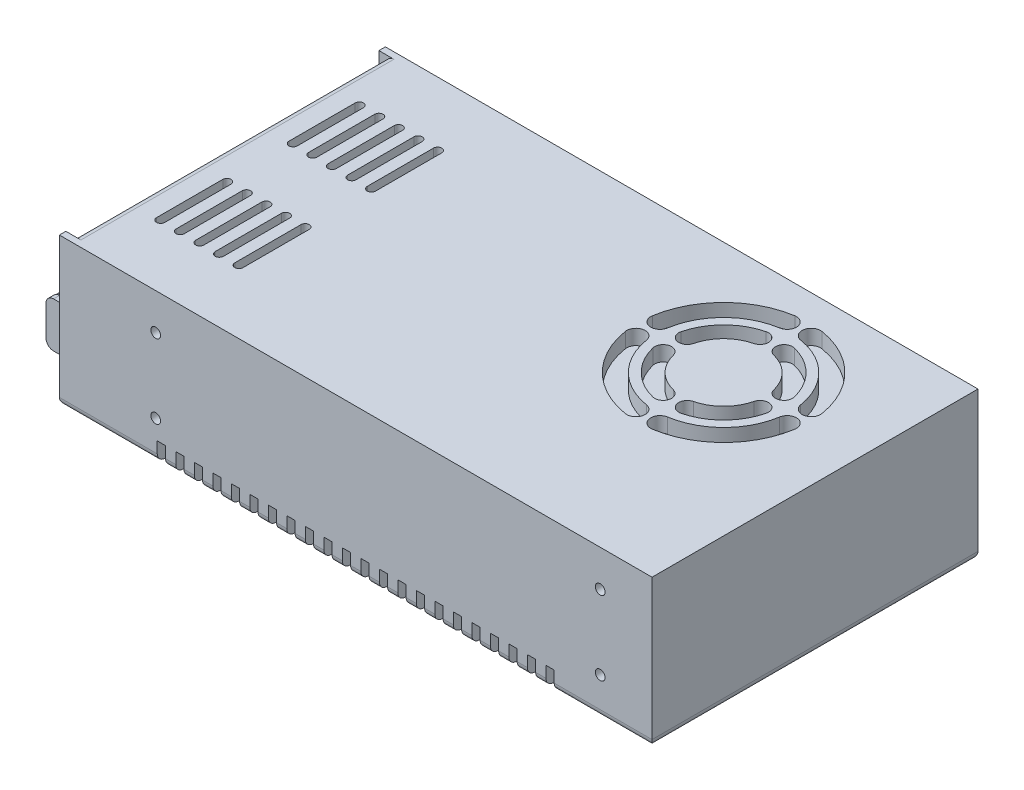
SolidWorks part; units mm, degrees
ref_plane "Front Plane" through (0, 0, 0) normal (0, 0, 1) x (1, 0, 0)
ref_plane "Top Plane" through (0, 0, 0) normal (0, 1, 0) x (1, 0, 0)
ref_plane "Right Plane" through (0, 0, 0) normal (1, 0, 0) x (0, 0, -1)
sketch "Sketch1" plane through (0, 0, 0) normal (0, 1, 0) x (1, 0, 0)
  line L1 (-100, -55) -> (100, -55)
  line L2 (-100, -55) -> (-100, 55)
  line L3 (-100, 55) -> (100, 55)
  line L4 (100, -55) -> (100, 55)
  line L5 (-100, -55) -> (100, 55) construction
  line L6 (-100, 55) -> (100, -55) construction
  point P0 (0, 0)
  dimension "D1" = 110
  dimension "D2" = 200
extrude "Boss-Extrude1" add sketch "Sketch1" along normal blind 50
sketch "Sketch2" plane through (0, 50, 0) normal (0, 1, 0) x (1, 0, 0)
  line L0 (-100, 55) -> (-100, -55) construction
  line L1 (-100, 52.8156) -> (-97.46, 52.8156)
  line L2 (-100, 52.8156) -> (-100, -52.8156)
  line L3 (-100, -52.8156) -> (-97.46, -52.8156)
  line L4 (-97.46, 52.8156) -> (-97.46, -52.8156)
  line L5 (-100, -55) -> (100, -55) construction
  line L6 (100, 55) -> (-100, 55) construction
  dimension "D1" = 2.1844
  dimension "D2" = 2.1844
  dimension "D3" = 2.54
extrude "Cut-Extrude1" cut sketch "Sketch2" against normal blind 41.91
sketch "Sketch3" plane through (-97.46, 0, 0) normal (-1, 0, 0) x (0, 0, 1)
  line L1 (-40.3008, 24.4602) -> (49.1072, 24.4602)
  line L2 (-40.3008, 24.4602) -> (-40.3008, 9.2202)
  line L3 (-40.3008, 9.2202) -> (49.1072, 9.2202)
  line L4 (49.1072, 24.4602) -> (49.1072, 9.2202)
  line L7 (-55, 0) -> (55, 0) construction
  line L8 (55, 50) -> (55, 0) construction
  dimension "D1" = 9.2202
  dimension "D2" = 5.8928
  dimension "D3" = 15.24
  dimension "D4" = 89.408
extrude "Boss-Extrude2" add sketch "Sketch3" along normal blind 12.7
sketch "Sketch4" plane through (-97.46, 0, 0) normal (-1, 0, 0) x (0, 0, 1)
  line L0 (-52.8156, 8.09) -> (-52.8156, 50) construction
  line L1 (-40.3008, 9.2202) -> (-52.8156, 9.2202)
  line L2 (49.1072, 9.2202) -> (49.1072, 24.4602)
  line L3 (49.1072, 24.4602) -> (-40.3008, 24.4602)
  line L4 (-52.8156, 9.2202) -> (-52.8156, 27.0002)
  line L5 (-52.8156, 27.0002) -> (52.8156, 27.0002)
  line L6 (52.8156, 8.09) -> (52.8156, 50) construction
  line L7 (52.8156, 27.0002) -> (52.8156, 9.2202)
  line L8 (52.8156, 9.2202) -> (49.1072, 9.2202)
  line L9 (-40.3008, 24.4602) -> (-40.3008, 9.2202)
  dimension "D1" = 17.78
extrude "Cut-Extrude3" cut sketch "Sketch4" against normal blind 25.4 contours L5 L7 L8 L2 L3 L9 L1 L4
sketch "Sketch5" plane through (0, 9.2202, 0) normal (0, 1, 0) x (1, 0, 0)
  line L0 (-97.46, 40.3008) -> (-97.46, 52.8156) construction
  line L1 (-96.19, 45.7036) -> (-89.84, 45.7036)
  line L2 (-96.19, 45.7036) -> (-96.19, 36.8136)
  line L3 (-96.19, 36.8136) -> (-89.84, 36.8136)
  line L4 (-89.84, 45.7036) -> (-89.84, 36.8136)
  dimension "D1" = 6.35
  dimension "D2" = 1.27
  dimension "D3" = 8.89
  dimension "D4" = 7.112
extrude "Boss-Extrude3" add sketch "Sketch5" along normal blind 8.89
sketch "Sketch6" plane through (0, 24.4602, 0) normal (0, 1, 0) x (1, 0, 0)
  line L0 (-110.16, -49.1072) -> (-110.16, 40.3008) construction
  line L1 (-110.16, 38.2688) -> (-102.032, 38.2688)
  line L2 (-110.16, 38.2688) -> (-110.16, 30.1408)
  line L3 (-110.16, 30.1408) -> (-102.032, 30.1408)
  line L4 (-102.032, 38.2688) -> (-102.032, 30.1408)
  line L5 (-110.16, 40.3008) -> (-72.06, 40.3008) construction
  line L6 (-110.16, 28.6168) -> (-102.032, 28.6168)
  line L7 (-110.16, 28.6168) -> (-110.16, 20.4888)
  line L8 (-110.16, 20.4888) -> (-102.032, 20.4888)
  line L9 (-102.032, 28.6168) -> (-102.032, 20.4888)
  line L10 (-110.16, 18.9648) -> (-102.032, 18.9648)
  line L11 (-110.16, 18.9648) -> (-110.16, 10.8368)
  line L12 (-110.16, 10.8368) -> (-102.032, 10.8368)
  line L13 (-102.032, 18.9648) -> (-102.032, 10.8368)
  line L14 (-110.16, 9.3128) -> (-102.032, 9.3128)
  line L15 (-110.16, 9.3128) -> (-110.16, 1.1848)
  line L16 (-110.16, 1.1848) -> (-102.032, 1.1848)
  line L17 (-102.032, 9.3128) -> (-102.032, 1.1848)
  line L18 (-110.16, -0.3392) -> (-102.032, -0.3392)
  line L19 (-110.16, -0.3392) -> (-110.16, -8.4672)
  line L20 (-110.16, -8.4672) -> (-102.032, -8.4672)
  line L21 (-102.032, -0.3392) -> (-102.032, -8.4672)
  line L22 (-110.16, -9.9912) -> (-102.032, -9.9912)
  line L23 (-110.16, -9.9912) -> (-110.16, -18.1192)
  line L24 (-110.16, -18.1192) -> (-102.032, -18.1192)
  line L25 (-102.032, -9.9912) -> (-102.032, -18.1192)
  line L26 (-110.16, -19.6432) -> (-102.032, -19.6432)
  line L27 (-110.16, -19.6432) -> (-110.16, -27.7712)
  line L28 (-110.16, -27.7712) -> (-102.032, -27.7712)
  line L29 (-102.032, -19.6432) -> (-102.032, -27.7712)
  line L30 (-110.16, -29.2952) -> (-102.032, -29.2952)
  line L31 (-110.16, -29.2952) -> (-110.16, -37.4232)
  line L32 (-110.16, -37.4232) -> (-102.032, -37.4232)
  line L33 (-102.032, -29.2952) -> (-102.032, -37.4232)
  line L35 (-110.16, -38.9472) -> (-102.032, -38.9472)
  line L36 (-110.16, -38.9472) -> (-110.16, -47.0752)
  line L37 (-110.16, -47.0752) -> (-102.032, -47.0752)
  line L38 (-102.032, -38.9472) -> (-102.032, -47.0752)
  line L39 (-110.16, -49.1072) -> (-72.06, -49.1072) construction
  dimension "D1" = 2.032
  dimension "D2" = 8.128
  dimension "D3" = 8.128
  dimension "D5" = 2.032
  dimension "D4" = 9
extrude "Cut-Extrude4" cut sketch "Sketch6" against normal through all
sketch "Sketch8" plane through (-102.032, 0, 0) normal (-1, 0, 0) x (0, 0, 1)
  line L0 (-30.1408, 9.2202) -> (-38.2688, 9.2202) construction
  line L2 (47.0752, 24.4602) -> (38.9472, 24.4602) construction
  circle A0 centre (-34.2048, 16.8402) radius 1.905
  circle A1 centre (-24.5528, 16.8402) radius 1.905
  circle A2 centre (-14.9008, 16.8402) radius 1.905
  circle A3 centre (-5.2488, 16.8402) radius 1.905
  circle A4 centre (4.4032, 16.8402) radius 1.905
  circle A5 centre (14.0552, 16.8402) radius 1.905
  circle A6 centre (23.7072, 16.8402) radius 1.905
  circle A7 centre (33.3592, 16.8402) radius 1.905
  circle A8 centre (43.0112, 16.8402) radius 1.905
  point P4 (-34.2048, 9.2202)
  point P23 (43.0112, 24.4602)
  dimension "D1" = 3.81
  dimension "D2" = 7.62
  dimension "D3" = 9
extrude "Boss-Extrude4" add sketch "Sketch8" along normal blind 2.54
sketch "Sketch9" plane through (-104.572, 0, 0) normal (-1, 0, 0) x (0, 0, 1)
  circle A0 centre (-34.2048, 16.8402) radius 3.81
  circle A1 centre (-24.5528, 16.8402) radius 3.81
  circle A2 centre (-14.9008, 16.8402) radius 3.81
  circle A3 centre (-5.2488, 16.8402) radius 3.81
  circle A4 centre (4.4032, 16.8402) radius 3.81
  circle A5 centre (14.0552, 16.8402) radius 3.81
  circle A6 centre (23.7072, 16.8402) radius 3.81
  circle A7 centre (33.3592, 16.8402) radius 3.81
  circle A12 centre (43.0112, 16.8402) radius 3.81
  dimension "D1" = 7.62
extrude "Boss-Extrude5" add sketch "Sketch9" along normal blind 3.81
fillet "Fillet1" radius 1.27 9 edges at (-108.382, 16.8402, -30.3948) (-108.382, 16.8402, 8.2132) (-108.382, 16.8402, 46.8212) (-108.382, 16.8402, 37.1692) (-108.382, 16.8402, 27.5172) (-108.382, 16.8402, 17.8652) (-108.382, 16.8402, -1.4388) (-108.382, 16.8402, -11.0908) (-108.382, 16.8402, -20.7428)
sketch "Sketch10" plane through (0, 50, 0) normal (0, 1, 0) x (1, 0, 0)
  line L0 (100, 55) -> (-100, 55) construction
  line L1 (100, -55) -> (100, 55) construction
  line L2 (77.771, 20.964) -> (77.771, 12.836) construction
  line L3 (52.248, 48.006) -> (52.248, -12.056) construction
  line L4 (77.771, 16.9) -> (52.248, 16.9) construction
  line L5 (56.312, 42.423) -> (48.184, 42.423) construction
  line L6 (26.725, 20.964) -> (26.725, 12.836) construction
  arc A0 (65.8045, 20.2739) -> (55.6219, 30.4565) centre (52.248, 16.9) ccw
  arc A1 (71.3503, 21.6541) -> (57.0021, 36.0023) centre (52.248, 16.9) ccw
  arc A2 (74.6982, 20.4747) -> (55.8227, 39.3502) centre (52.248, 16.9) ccw
  arc A3 (80.8438, 21.4533) -> (56.8013, 45.4958) centre (52.248, 16.9) ccw
  arc A4 (74.6982, 20.4747) -> (80.8438, 21.4533) centre (77.771, 20.964) ccw
  arc A5 (56.8013, 45.4958) -> (55.8227, 39.3502) centre (56.312, 42.423) ccw
  arc A6 (57.0021, 36.0023) -> (55.6219, 30.4565) centre (56.312, 33.2294) ccw
  arc A7 (65.8045, 13.5261) -> (71.3503, 12.1459) centre (68.5774, 12.836) cw
  arc A8 (65.8045, 20.2739) -> (71.3503, 21.6541) centre (68.5774, 20.964) ccw
  arc A9 (57.0021, -2.2023) -> (55.6219, 3.3435) centre (56.312, 0.5706) cw
  arc A10 (56.8013, -11.6958) -> (55.8227, -5.5502) centre (56.312, -8.623) cw
  arc A11 (74.6982, 13.3253) -> (80.8438, 12.3467) centre (77.771, 12.836) cw
  arc A12 (80.8438, 12.3467) -> (56.8013, -11.6958) centre (52.248, 16.9) cw
  arc A13 (74.6982, 13.3253) -> (55.8227, -5.5502) centre (52.248, 16.9) cw
  arc A14 (71.3503, 12.1459) -> (57.0021, -2.2023) centre (52.248, 16.9) cw
  arc A15 (65.8045, 13.5261) -> (55.6219, 3.3435) centre (52.248, 16.9) cw
  arc A16 (38.6915, 13.5261) -> (48.8741, 3.3435) centre (52.248, 16.9) ccw
  arc A17 (33.1457, 12.1459) -> (47.4939, -2.2023) centre (52.248, 16.9) ccw
  arc A18 (29.7978, 13.3253) -> (48.6733, -5.5502) centre (52.248, 16.9) ccw
  arc A19 (23.6522, 12.3467) -> (47.6947, -11.6958) centre (52.248, 16.9) ccw
  arc A20 (29.7978, 13.3253) -> (23.6522, 12.3467) centre (26.725, 12.836) ccw
  arc A21 (47.6947, -11.6958) -> (48.6733, -5.5502) centre (48.184, -8.623) ccw
  arc A22 (47.4939, -2.2023) -> (48.8741, 3.3435) centre (48.184, 0.5706) ccw
  arc A23 (38.6915, 20.2739) -> (33.1457, 21.6541) centre (35.9186, 20.964) cw
  arc A24 (38.6915, 13.5261) -> (33.1457, 12.1459) centre (35.9186, 12.836) ccw
  arc A25 (47.4939, 36.0023) -> (48.8741, 30.4565) centre (48.184, 33.2294) cw
  arc A26 (47.6947, 45.4958) -> (48.6733, 39.3502) centre (48.184, 42.423) cw
  arc A27 (29.7978, 20.4747) -> (23.6522, 21.4533) centre (26.725, 20.964) cw
  arc A28 (23.6522, 21.4533) -> (47.6947, 45.4958) centre (52.248, 16.9) cw
  arc A29 (29.7978, 20.4747) -> (48.6733, 39.3502) centre (52.248, 16.9) cw
  arc A30 (33.1457, 21.6541) -> (47.4939, 36.0023) centre (52.248, 16.9) cw
  arc A31 (38.6915, 20.2739) -> (48.8741, 30.4565) centre (52.248, 16.9) cw
  point P6 (52.248, 42.423)
  dimension "D1" = 38.1
  dimension "D3" = 27.94
  dimension "D4" = 39.37
  dimension "D5" = 3.048
  dimension "D6" = 57.912
  dimension "D7" = 8.128
  dimension "D2" = 47.752
extrude "Cut-Extrude6" cut sketch "Sketch10" against normal blind 5.08
sketch "Sketch11" plane through (0, 50, 0) normal (0, 1, 0) x (1, 0, 0)
  line L0 (-87.3, 33.528) -> (-87.3, 11.176) construction
  line L1 (-85.903, 33.528) -> (-85.903, 11.176)
  line L2 (-88.697, 33.528) -> (-88.697, 11.176)
  line L3 (-87.3, -11.176) -> (-87.3, -33.528) construction
  line L4 (-85.903, -11.176) -> (-85.903, -33.528)
  line L5 (-88.697, -11.176) -> (-88.697, -33.528)
  line L6 (-97.46, 0) -> (100, 0) construction
  line L7 (-97.46, -52.8156) -> (-97.46, 52.8156) construction
  line L8 (100, -55) -> (100, 55) construction
  line L9 (-87.3, 11.176) -> (-87.3, -11.176) construction
  line L10 (-80.696, 11.176) -> (-80.696, -11.176) construction
  line L11 (-80.696, 33.528) -> (-80.696, 11.176) construction
  line L12 (-79.299, 33.528) -> (-79.299, 11.176)
  line L13 (-82.093, 33.528) -> (-82.093, 11.176)
  line L14 (-80.696, -11.176) -> (-80.696, -33.528) construction
  line L15 (-79.299, -11.176) -> (-79.299, -33.528)
  line L16 (-82.093, -11.176) -> (-82.093, -33.528)
  line L17 (-74.092, 11.176) -> (-74.092, -11.176) construction
  line L18 (-74.092, 33.528) -> (-74.092, 11.176) construction
  line L19 (-72.695, 33.528) -> (-72.695, 11.176)
  line L20 (-75.489, 33.528) -> (-75.489, 11.176)
  line L21 (-74.092, -11.176) -> (-74.092, -33.528) construction
  line L22 (-72.695, -11.176) -> (-72.695, -33.528)
  line L23 (-75.489, -11.176) -> (-75.489, -33.528)
  line L24 (-67.488, 11.176) -> (-67.488, -11.176) construction
  line L25 (-67.488, 33.528) -> (-67.488, 11.176) construction
  line L26 (-66.091, 33.528) -> (-66.091, 11.176)
  line L27 (-68.885, 33.528) -> (-68.885, 11.176)
  line L28 (-67.488, -11.176) -> (-67.488, -33.528) construction
  line L29 (-66.091, -11.176) -> (-66.091, -33.528)
  line L30 (-68.885, -11.176) -> (-68.885, -33.528)
  line L31 (-60.884, 11.176) -> (-60.884, -11.176) construction
  line L32 (-60.884, 33.528) -> (-60.884, 11.176) construction
  line L33 (-59.487, 33.528) -> (-59.487, 11.176)
  line L34 (-62.281, 33.528) -> (-62.281, 11.176)
  line L35 (-60.884, -11.176) -> (-60.884, -33.528) construction
  line L36 (-59.487, -11.176) -> (-59.487, -33.528)
  line L37 (-62.281, -11.176) -> (-62.281, -33.528)
  arc A0 (-85.903, 33.528) -> (-88.697, 33.528) centre (-87.3, 33.528) ccw
  arc A1 (-88.697, 11.176) -> (-85.903, 11.176) centre (-87.3, 11.176) ccw
  arc A2 (-85.903, -11.176) -> (-88.697, -11.176) centre (-87.3, -11.176) ccw
  arc A3 (-88.697, -33.528) -> (-85.903, -33.528) centre (-87.3, -33.528) ccw
  arc A4 (-79.299, 33.528) -> (-82.093, 33.528) centre (-80.696, 33.528) ccw
  arc A5 (-82.093, 11.176) -> (-79.299, 11.176) centre (-80.696, 11.176) ccw
  arc A6 (-79.299, -11.176) -> (-82.093, -11.176) centre (-80.696, -11.176) ccw
  arc A7 (-82.093, -33.528) -> (-79.299, -33.528) centre (-80.696, -33.528) ccw
  arc A8 (-72.695, 33.528) -> (-75.489, 33.528) centre (-74.092, 33.528) ccw
  arc A9 (-75.489, 11.176) -> (-72.695, 11.176) centre (-74.092, 11.176) ccw
  arc A10 (-72.695, -11.176) -> (-75.489, -11.176) centre (-74.092, -11.176) ccw
  arc A11 (-75.489, -33.528) -> (-72.695, -33.528) centre (-74.092, -33.528) ccw
  arc A12 (-66.091, 33.528) -> (-68.885, 33.528) centre (-67.488, 33.528) ccw
  arc A13 (-68.885, 11.176) -> (-66.091, 11.176) centre (-67.488, 11.176) ccw
  arc A14 (-66.091, -11.176) -> (-68.885, -11.176) centre (-67.488, -11.176) ccw
  arc A15 (-68.885, -33.528) -> (-66.091, -33.528) centre (-67.488, -33.528) ccw
  arc A16 (-59.487, 33.528) -> (-62.281, 33.528) centre (-60.884, 33.528) ccw
  arc A17 (-62.281, 11.176) -> (-59.487, 11.176) centre (-60.884, 11.176) ccw
  arc A18 (-59.487, -11.176) -> (-62.281, -11.176) centre (-60.884, -11.176) ccw
  arc A19 (-62.281, -33.528) -> (-59.487, -33.528) centre (-60.884, -33.528) ccw
  point P2 (-87.3, 22.352)
  point P7 (-87.3, -22.352)
  point P22 (-87.3, 0)
  point P26 (-80.696, 22.352)
  point P31 (-80.696, -22.352)
  point P42 (-74.092, 22.352)
  point P47 (-74.092, -22.352)
  point P58 (-67.488, 22.352)
  point P63 (-67.488, -22.352)
  point P74 (-60.884, 22.352)
  point P79 (-60.884, -22.352)
  dimension "D1" = 22.352
  dimension "D2" = 22.352
  dimension "D3" = 10.16
  dimension "D4" = 2.794
  dimension "D6" = 6.604
  dimension "D5" = 5
extrude "Cut-Extrude7" cut sketch "Sketch11" against normal blind 5.08
fillet "Fillet2" radius 2.54 5 edges at (0, 0, -55) (-100, 0, 0) (0, 0, 55) (100, 0, 0) (-97.46, 50, 0)
sketch "Sketch12" plane through (0, 0, 0) normal (0, -1, 0) x (1, 0, 0)
  line L0 (65.583, 37.982) -> (65.583, 55) construction
  line L1 (-100, 55) -> (100, 55) construction
  line L2 (64.186, 37.982) -> (64.186, 55)
  line L3 (66.98, 37.982) -> (66.98, 55)
  line L4 (100, 55) -> (100, -55) construction
  line L5 (59.337, 37.982) -> (59.337, 55) construction
  line L6 (57.94, 37.982) -> (57.94, 55)
  line L7 (60.734, 37.982) -> (60.734, 55)
  line L8 (53.091, 37.982) -> (53.091, 55) construction
  line L9 (51.694, 37.982) -> (51.694, 55)
  line L10 (54.488, 37.982) -> (54.488, 55)
  line L11 (46.845, 37.982) -> (46.845, 55) construction
  line L12 (45.448, 37.982) -> (45.448, 55)
  line L13 (48.242, 37.982) -> (48.242, 55)
  line L14 (40.599, 37.982) -> (40.599, 55) construction
  line L15 (39.202, 37.982) -> (39.202, 55)
  line L16 (41.996, 37.982) -> (41.996, 55)
  line L17 (34.353, 37.982) -> (34.353, 55) construction
  line L18 (32.956, 37.982) -> (32.956, 55)
  line L19 (35.75, 37.982) -> (35.75, 55)
  line L20 (28.107, 37.982) -> (28.107, 55) construction
  line L21 (26.71, 37.982) -> (26.71, 55)
  line L22 (29.504, 37.982) -> (29.504, 55)
  line L23 (21.861, 37.982) -> (21.861, 55) construction
  line L24 (20.464, 37.982) -> (20.464, 55)
  line L25 (23.258, 37.982) -> (23.258, 55)
  line L26 (15.615, 37.982) -> (15.615, 55) construction
  line L27 (14.218, 37.982) -> (14.218, 55)
  line L28 (17.012, 37.982) -> (17.012, 55)
  line L29 (9.369, 37.982) -> (9.369, 55) construction
  line L30 (7.972, 37.982) -> (7.972, 55)
  line L31 (10.766, 37.982) -> (10.766, 55)
  line L32 (3.123, 37.982) -> (3.123, 55) construction
  line L33 (1.726, 37.982) -> (1.726, 55)
  line L34 (4.52, 37.982) -> (4.52, 55)
  line L35 (-3.123, 37.982) -> (-3.123, 55) construction
  line L36 (-4.52, 37.982) -> (-4.52, 55)
  line L37 (-1.726, 37.982) -> (-1.726, 55)
  line L38 (-9.369, 37.982) -> (-9.369, 55) construction
  line L39 (-10.766, 37.982) -> (-10.766, 55)
  line L40 (-7.972, 37.982) -> (-7.972, 55)
  line L41 (-15.615, 37.982) -> (-15.615, 55) construction
  line L42 (-17.012, 37.982) -> (-17.012, 55)
  line L43 (-14.218, 37.982) -> (-14.218, 55)
  line L44 (-21.861, 37.982) -> (-21.861, 55) construction
  line L45 (-23.258, 37.982) -> (-23.258, 55)
  line L46 (-20.464, 37.982) -> (-20.464, 55)
  line L47 (-28.107, 37.982) -> (-28.107, 55) construction
  line L48 (-29.504, 37.982) -> (-29.504, 55)
  line L49 (-26.71, 37.982) -> (-26.71, 55)
  line L50 (-34.353, 37.982) -> (-34.353, 55) construction
  line L51 (-35.75, 37.982) -> (-35.75, 55)
  line L52 (-32.956, 37.982) -> (-32.956, 55)
  line L53 (-40.599, 37.982) -> (-40.599, 55) construction
  line L54 (-41.996, 37.982) -> (-41.996, 55)
  line L55 (-39.202, 37.982) -> (-39.202, 55)
  line L56 (-46.845, 37.982) -> (-46.845, 55) construction
  line L57 (-48.242, 37.982) -> (-48.242, 55)
  line L58 (-45.448, 37.982) -> (-45.448, 55)
  line L59 (-53.091, 37.982) -> (-53.091, 55) construction
  line L60 (-54.488, 37.982) -> (-54.488, 55)
  line L61 (-51.694, 37.982) -> (-51.694, 55)
  line L62 (-59.337, 37.982) -> (-59.337, 55) construction
  line L63 (-60.734, 37.982) -> (-60.734, 55)
  line L64 (-57.94, 37.982) -> (-57.94, 55)
  line L65 (-65.583, 37.982) -> (-65.583, 55) construction
  line L66 (-66.98, 37.982) -> (-66.98, 55)
  line L67 (-64.186, 37.982) -> (-64.186, 55)
  line L68 (-100, -55) -> (-100, 55) construction
  arc A0 (64.186, 37.982) -> (66.98, 37.982) centre (65.583, 37.982) ccw
  arc A1 (66.98, 55) -> (64.186, 55) centre (65.583, 55) ccw
  arc A2 (57.94, 37.982) -> (60.734, 37.982) centre (59.337, 37.982) ccw
  arc A3 (60.734, 55) -> (57.94, 55) centre (59.337, 55) ccw
  arc A4 (51.694, 37.982) -> (54.488, 37.982) centre (53.091, 37.982) ccw
  arc A5 (54.488, 55) -> (51.694, 55) centre (53.091, 55) ccw
  arc A6 (45.448, 37.982) -> (48.242, 37.982) centre (46.845, 37.982) ccw
  arc A7 (48.242, 55) -> (45.448, 55) centre (46.845, 55) ccw
  arc A8 (39.202, 37.982) -> (41.996, 37.982) centre (40.599, 37.982) ccw
  arc A9 (41.996, 55) -> (39.202, 55) centre (40.599, 55) ccw
  arc A10 (32.956, 37.982) -> (35.75, 37.982) centre (34.353, 37.982) ccw
  arc A11 (35.75, 55) -> (32.956, 55) centre (34.353, 55) ccw
  arc A12 (26.71, 37.982) -> (29.504, 37.982) centre (28.107, 37.982) ccw
  arc A13 (29.504, 55) -> (26.71, 55) centre (28.107, 55) ccw
  arc A14 (20.464, 37.982) -> (23.258, 37.982) centre (21.861, 37.982) ccw
  arc A15 (23.258, 55) -> (20.464, 55) centre (21.861, 55) ccw
  arc A16 (14.218, 37.982) -> (17.012, 37.982) centre (15.615, 37.982) ccw
  arc A17 (17.012, 55) -> (14.218, 55) centre (15.615, 55) ccw
  arc A18 (7.972, 37.982) -> (10.766, 37.982) centre (9.369, 37.982) ccw
  arc A19 (10.766, 55) -> (7.972, 55) centre (9.369, 55) ccw
  arc A20 (1.726, 37.982) -> (4.52, 37.982) centre (3.123, 37.982) ccw
  arc A21 (4.52, 55) -> (1.726, 55) centre (3.123, 55) ccw
  arc A22 (-4.52, 37.982) -> (-1.726, 37.982) centre (-3.123, 37.982) ccw
  arc A23 (-1.726, 55) -> (-4.52, 55) centre (-3.123, 55) ccw
  arc A24 (-10.766, 37.982) -> (-7.972, 37.982) centre (-9.369, 37.982) ccw
  arc A25 (-7.972, 55) -> (-10.766, 55) centre (-9.369, 55) ccw
  arc A26 (-17.012, 37.982) -> (-14.218, 37.982) centre (-15.615, 37.982) ccw
  arc A27 (-14.218, 55) -> (-17.012, 55) centre (-15.615, 55) ccw
  arc A28 (-23.258, 37.982) -> (-20.464, 37.982) centre (-21.861, 37.982) ccw
  arc A29 (-20.464, 55) -> (-23.258, 55) centre (-21.861, 55) ccw
  arc A30 (-29.504, 37.982) -> (-26.71, 37.982) centre (-28.107, 37.982) ccw
  arc A31 (-26.71, 55) -> (-29.504, 55) centre (-28.107, 55) ccw
  arc A32 (-35.75, 37.982) -> (-32.956, 37.982) centre (-34.353, 37.982) ccw
  arc A33 (-32.956, 55) -> (-35.75, 55) centre (-34.353, 55) ccw
  arc A34 (-41.996, 37.982) -> (-39.202, 37.982) centre (-40.599, 37.982) ccw
  arc A35 (-39.202, 55) -> (-41.996, 55) centre (-40.599, 55) ccw
  arc A36 (-48.242, 37.982) -> (-45.448, 37.982) centre (-46.845, 37.982) ccw
  arc A37 (-45.448, 55) -> (-48.242, 55) centre (-46.845, 55) ccw
  arc A38 (-54.488, 37.982) -> (-51.694, 37.982) centre (-53.091, 37.982) ccw
  arc A39 (-51.694, 55) -> (-54.488, 55) centre (-53.091, 55) ccw
  arc A40 (-60.734, 37.982) -> (-57.94, 37.982) centre (-59.337, 37.982) ccw
  arc A41 (-57.94, 55) -> (-60.734, 55) centre (-59.337, 55) ccw
  arc A42 (-66.98, 37.982) -> (-64.186, 37.982) centre (-65.583, 37.982) ccw
  arc A43 (-64.186, 55) -> (-66.98, 55) centre (-65.583, 55) ccw
  point P4 (65.583, 46.491)
  point P15 (59.337, 46.491)
  point P22 (53.091, 46.491)
  point P29 (46.845, 46.491)
  point P36 (40.599, 46.491)
  point P43 (34.353, 46.491)
  point P50 (28.107, 46.491)
  point P57 (21.861, 46.491)
  point P64 (15.615, 46.491)
  point P71 (9.369, 46.491)
  point P78 (3.123, 46.491)
  point P85 (-3.123, 46.491)
  point P92 (-9.369, 46.491)
  point P99 (-15.615, 46.491)
  point P106 (-21.861, 46.491)
  point P113 (-28.107, 46.491)
  point P120 (-34.353, 46.491)
  point P127 (-40.599, 46.491)
  point P134 (-46.845, 46.491)
  point P141 (-53.091, 46.491)
  point P148 (-59.337, 46.491)
  point P155 (-65.583, 46.491)
  dimension "D1" = 1.397
  dimension "D2" = 17.018
  dimension "D3" = 33.02
  dimension "D5" = 33.02
  dimension "D4" = 22
extrude "Cut-Extrude8" cut sketch "Sketch12" against normal blind 6.35
mirror "Mirror1" about plane through (0, 0, 0) normal (0, 0, 1) of "Cut-Extrude8"
sketch "Sketch13" plane through (-110.16, 0, 0) normal (-1, 0, 0) x (0, 0, 1)
  line L1 (-40.3008, 9.2202) -> (49.1072, 9.2202)
  line L2 (-40.3008, 9.2202) -> (-40.3008, 24.4602)
  line L3 (-40.3008, 24.4602) -> (49.1072, 24.4602)
  line L4 (49.1072, 9.2202) -> (49.1072, 24.4602)
extrude "Boss-Extrude6" add sketch "Sketch13" along normal blind 0.254
fillet "Fillet3" radius 2.54 2 edges at (-110.414, 9.2202, 4.4032) (-110.414, 24.4602, 4.4032)
sketch "Sketch14" plane through (-97.46, 0, 0) normal (-1, 0, 0) x (0, 0, 1)
  line L0 (-52.8156, 33.3502) -> (52.8156, 33.3502) construction
  line L1 (-52.8156, 27.0002) -> (52.8156, 27.0002) construction
  line L2 (-52.8156, 8.09) -> (-52.8156, 50) construction
  line L3 (52.8156, 27.0002) -> (52.8156, 47.46) construction
  text T0 "  V          +V            -V        =   N  L" font "Century Gothic" height in points 18
  text T1 "      adj                      |                  |"
  dimension "D1" = 6.35
extrude "Cut-Extrude9" cut sketch "Sketch14" against normal blind 0.254
hole_wizard "M4x0.7 Tapped Hole1" positions "Sketch16" profile "Sketch15" tap size "M4x0.7" standard "ANSI Metric"
sketch "Sketch16" plane through (0, 0, -55) normal (0, 0, -1) x (-1, 0, 0)
  line L0 (-100, 50) -> (-100, 2.54) construction
  line L1 (100, 50) -> (100, 2.54) construction
  line L2 (97.46, 0) -> (66.98, 0) construction
  point P0 (68.25, 12.7)
  point P2 (-68.25, 12.7)
  dimension "D1" = 31.75
  dimension "D2" = 31.75
  dimension "D3" = 12.7
sketch "Sketch15" plane through (-68.25, 12.7, -55) normal (1, 0, 0) x (0, 1, 0)
  line L0 (0, 0) -> (0, 10.8974)
  line L1 (0, 10.8974) -> (1.65, 9.906)
  line L2 (1.65, 9.906) -> (1.65, 0)
  line L5 (1.65, 0) -> (0, 0)
  line L10 (0, 10.8974) -> (-1.65, 9.906) construction
  line L11 (0, -6.35) -> (0, 107.95) construction
  dimension "Tap Drill Dia." = 3.3
  dimension "Tap Drill Depth" = 9.906
  dimension "Drill Angle" = 118
hole_wizard "M4x0.7 Tapped Hole2" positions "Sketch18" profile "Sketch17" tap size "M4x0.7" standard "ANSI Metric"
sketch "Sketch18" plane through (0, 0, 55) normal (0, 0, 1) x (1, 0, 0)
  line L0 (97.46, 0) -> (66.98, 0) construction
  line L2 (-100, 50) -> (-100, 2.54) construction
  line L3 (-66.98, 0) -> (-97.46, 0) construction
  point P0 (82.5, 12.7)
  point P2 (82.5, 37.7)
  point P4 (-67.5, 37.7)
  point P6 (-67.5, 12.7)
  dimension "D1" = 12.7
  dimension "D2" = 150
  dimension "D3" = 25
  dimension "D4" = 32.5
  dimension "D5" = 12.7
sketch "Sketch17" plane through (82.5, 12.7, 55) normal (1, 0, 0) x (0, -1, 0)
  line L0 (0, 0) -> (0, 10.8974)
  line L1 (0, 10.8974) -> (1.65, 9.906)
  line L2 (1.65, 9.906) -> (1.65, 0)
  line L5 (1.65, 0) -> (0, 0)
  line L10 (0, 10.8974) -> (-1.65, 9.906) construction
  line L11 (0, -6.35) -> (0, 107.95) construction
  dimension "Tap Drill Dia." = 3.3
  dimension "Tap Drill Depth" = 9.906
  dimension "Drill Angle" = 118
hole_wizard "M4x0.7 Tapped Hole3" positions "Sketch20" profile "Sketch19" tap size "M4x0.7" standard "ANSI Metric"
sketch "Sketch20" plane through (0, 0, 0) normal (0, -1, 0) x (-1, 0, 0)
  line L4 (-100, 55) -> (-66.98, 55) construction
  line L5 (100, 55) -> (100, -55) construction
  point P0 (-82.5, -27.5)
  point P2 (-82.5, 22.5)
  point P4 (67.5, 22.5)
  point P6 (67.5, -27.5)
  dimension "D1" = 50
  dimension "D2" = 150
  dimension "D3" = 32.5
  dimension "D4" = 32.5
sketch "Sketch19" plane through (82.5, 0, 27.5) normal (1, 0, 0) x (0, 0, -1)
  line L0 (0, 0) -> (0, 10.8974)
  line L1 (0, 10.8974) -> (1.65, 9.906)
  line L2 (1.65, 9.906) -> (1.65, 0)
  line L5 (1.65, 0) -> (0, 0)
  line L10 (0, 10.8974) -> (-1.65, 9.906) construction
  line L11 (0, -6.35) -> (0, 107.95) construction
  dimension "Tap Drill Dia." = 3.3
  dimension "Tap Drill Depth" = 9.906
  dimension "Drill Angle" = 118
sketch "Sketch21" plane through (-100, 0, 0) normal (-1, 0, 0) x (0, 0, 1)
  line L0 (55, 24.6) -> (55, 40.475)
  line L1 (55, 50) -> (55, 2.54) construction
  line L2 (55, 40.475) -> (60, 43.1)
  line L3 (60, 43.1) -> (62.2465, 43.1)
  line L4 (62.2465, 43.1) -> (62.7715, 42.1)
  line L5 (62.7715, 42.1) -> (64.2929, 42.1)
  line L6 (64.2929, 42.1) -> (65.2929, 43.1)
  line L7 (64.7071, 41.1) -> (66, 42.3929)
  line L8 (64.7071, 41.1) -> (62.1671, 41.1)
  line L9 (62.1671, 41.1) -> (61.6421, 42.1)
  line L10 (61.6421, 42.1) -> (60.2465, 42.1)
  line L11 (60.2465, 42.1) -> (56, 39.8706)
  line L12 (56, 39.8706) -> (56, 24.6)
  line L13 (56, 24.6) -> (55, 24.6)
  line L14 (66, 42.3929) -> (65.2929, 43.1)
  line L15 (52.8156, 50) -> (55, 50) construction
  dimension "D1" = 15.875
  dimension "D2" = 1
  dimension "D3" = 16.5
  dimension "D4" = 1
  dimension "D5" = 1
  dimension "D6" = 1
  dimension "D7" = 1
  dimension "D8" = 1
  dimension "D9" = 11
  dimension "D10" = 5
  dimension "D11" = 17.5
  dimension "D12" = 135
  dimension "D13" = 25.4
  dimension "D14" = 2.54
extrude "Boss-Extrude7" [suppressed] add sketch "Sketch21" against normal blind 12.7 from offset 25.4 offset against normal yes
ref_plane "Plane1" through (0, 0, 0) normal (-1, 0, 0) x (0, 0, 1)
mirror "Mirror6" [suppressed] about plane through (0, 0, 0) normal (-1, 0, 0)
mirror "Mirror2" [suppressed]
